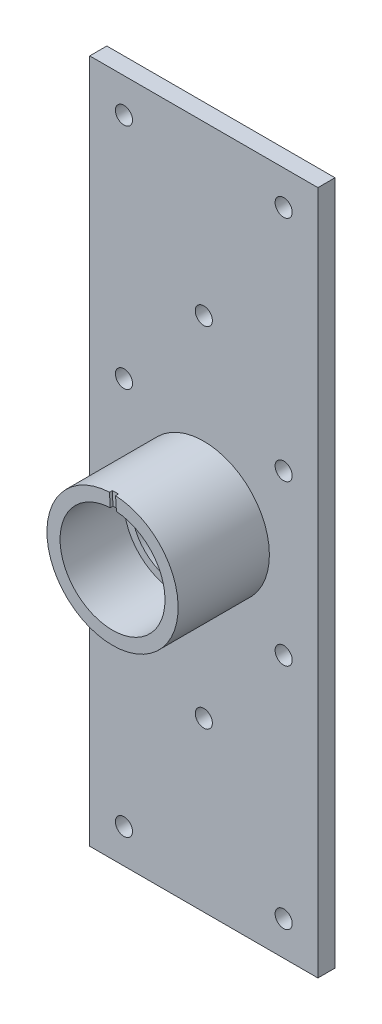
SolidWorks part; units mm, degrees
ref_plane "Front Plane" through (0, 0, 0) normal (0, 0, 1) x (1, 0, 0)
ref_plane "Top Plane" through (0, 0, 0) normal (0, 1, 0) x (1, 0, 0)
ref_plane "Right Plane" through (0, 0, 0) normal (1, 0, 0) x (0, 0, -1)
sketch "Sketch1" plane through (0, 0, 0) normal (0, 0, 1) x (1, 0, 0)
  line L5 (-31.75, 95.25) -> (31.75, 95.25)
  line L6 (-31.75, 95.25) -> (-31.75, -95.25)
  line L7 (-31.75, -95.25) -> (31.75, -95.25)
  line L8 (31.75, 95.25) -> (31.75, -95.25)
  line L9 (-31.75, 95.25) -> (31.75, -95.25) construction
  line L10 (-31.75, -95.25) -> (31.75, 95.25) construction
  point P5 (0, 0)
  dimension "D1" = 63.5
  dimension "D2" = 190.5
extrude "Boss-Extrude1" add sketch "Sketch1" along normal blind 4.7625
sketch "Sketch3" plane through (0, 0, 4.7625) normal (0, 0, 1) x (1, 0, 0)
  circle A0 centre (0, 0) radius 6.35
  dimension "D1" = 12.7
extrude "Cut-Extrude1" cut sketch "Sketch3" against normal blind 0.508
sketch "Sketch4" plane through (0, 0, 4.7625) normal (0, 0, 1) x (1, 0, 0)
  circle A0 centre (0, 0) radius 18.2562
  dimension "D1" = 36.5125
extrude "Boss-Extrude2" add sketch "Sketch4" along normal blind 38.1 contours A0
sketch "Sketch5" plane through (0, 0, 42.8625) normal (0, 0, 1) x (1, 0, 0)
  circle A0 centre (0, 0) radius 12.4619
  dimension "D1" = 24.9237
extrude "Cut-Extrude2" cut sketch "Sketch5" against normal blind 38.1 contours A0
sketch "Sketch7" plane through (0, 0, 42.8625) normal (0, 0, 1) x (1, 0, 0)
  circle A0 centre (0, 0) radius 14.2875
  dimension "D1" = 28.575
extrude "Cut-Extrude3" cut sketch "Sketch7" against normal blind 30.48
hole_wizard "3/16 (0.1875) Diameter Hole1" positions "Sketch8" profile "Sketch9" hole size "3/16" standard "ANSI Inch" end condition through all
sketch "Sketch8" plane through (0, 0, 4.7625) normal (0, 0, 1) x (1, 0, 0)
  line L0 (31.75, 95.25) -> (-31.75, 95.25) construction
  line L1 (31.75, -95.25) -> (31.75, 95.25) construction
  line L2 (-31.75, 95.25) -> (-31.75, -95.25) construction
  line L3 (-31.75, -95.25) -> (31.75, -95.25) construction
  point P0 (-22.225, 85.725)
  point P2 (-22.225, -85.725)
  point P4 (22.225, -85.725)
  point P6 (22.225, 85.725)
  point P17 (0, 48.514)
  point P19 (0, -48.514)
  point P23 (-22.225, 22.225)
  point P26 (-22.225, -22.225)
  point P28 (22.225, -22.225)
  point P30 (22.225, 22.225)
  dimension "D1" = 9.525
  dimension "D2" = 9.525
  dimension "D3" = 9.525
  dimension "D4" = 9.525
  dimension "D5" = 9.525
  dimension "D6" = 9.525
  dimension "D7" = 9.525
  dimension "D8" = 9.525
  dimension "D9" = 48.514
  dimension "D10" = 48.514
  dimension "D11" = 63.5
  dimension "D12" = 63.5
  dimension "D13" = 63.5
  dimension "D14" = 63.5
sketch "Sketch9" plane through (-22.225, 85.725, 4.7625) normal (1, 0, 0) x (0, -1, 0)
  line L0 (0, 0) -> (0, 4.7625)
  line L1 (0, 4.7625) -> (2.3812, 4.7625)
  line L2 (2.3812, 4.7625) -> (2.3812, 0)
  line L5 (2.3812, 0) -> (0, 0)
  line L11 (0, -6.35) -> (0, 107.95) construction
  dimension "Thru Hole Dia." = 4.7625
  dimension "Thru Hole Depth" = 4.7625
sketch "Sketch10" plane through (0, 0, 4.7625) normal (0, 0, 1) x (1, 0, 0)
  line L0 (31.75, 31.75) -> (-31.75, 31.75)
  line L1 (31.75, -95.25) -> (31.75, 95.25) construction
  line L2 (-31.75, 95.25) -> (-31.75, -95.25) construction
  line L3 (31.75, -31.75) -> (-31.75, -31.75)
  point P8 (-31.75, 0)
  dimension "D1" = 31.75
  dimension "D2" = 31.75
sketch "Sketch13" plane through (0, 0, 42.8625) normal (0, 0, 1) x (1, 0, 0)
  circle A0 centre (0, 0) radius 14.605
  dimension "D1" = 29.21
extrude "Cut-Extrude4" cut sketch "Sketch13" against normal up to surface (30.48 mm away) up to face at (14.2875, 0, 12.3825)
sketch "Sketch14" plane through (0, 0, 42.8625) normal (0, 0, 1) x (1, 0, 0)
  circle A0 centre (0, 0) radius 18.2562
extrude "Cut-Extrude5" cut sketch "Sketch14" against normal blind 12.7
sketch "Sketch15" plane through (0, 0, 30.1625) normal (0, 0, 1) x (1, 0, 0)
  line L0 (0.8404, 18.2369) -> (1.082, 14.5649)
  line L1 (-0.8423, 18.2368) -> (-0.6739, 14.5894)
  circle A0 centre (0, 0) radius 18.2562 construction
  circle A1 centre (0, 0) radius 14.605 construction
  arc A2 (1.082, 14.5649) -> (-0.6739, 14.5894) centre (0, 0) ccw
  arc A3 (0.8404, 18.2369) -> (-0.8423, 18.2368) centre (0, 0) ccw
extrude "Cut-Extrude9" cut sketch "Sketch15" against normal blind 0.7937
